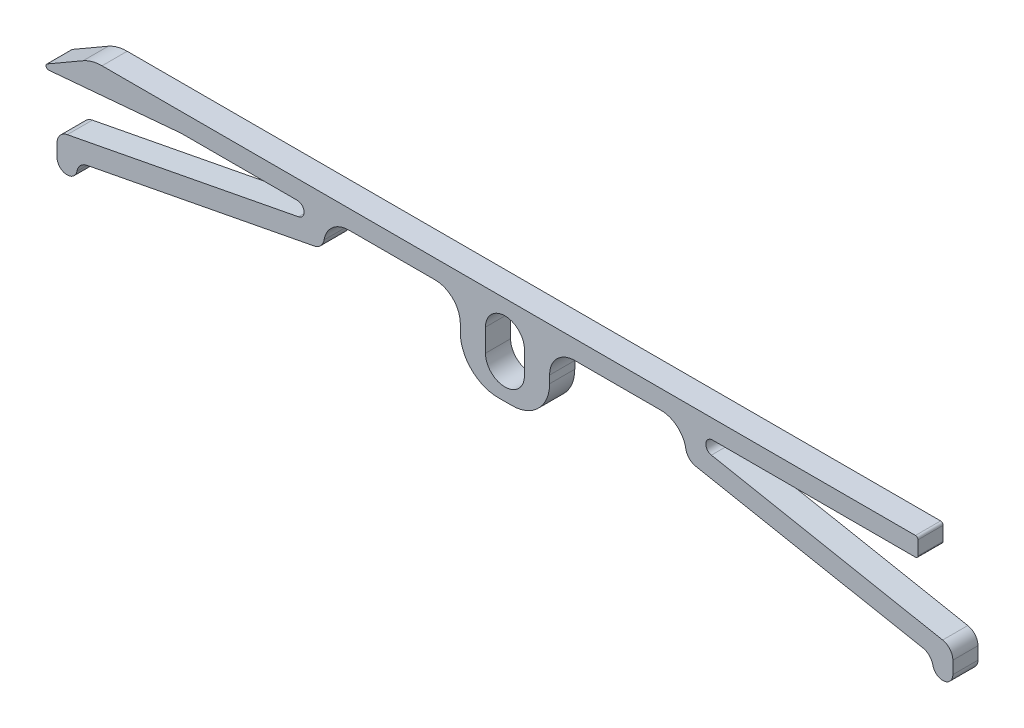
SolidWorks part; units mm, degrees
other "Static 1"
material "AISI 304"
ref_plane "Front Plane" through (0, 0, 0) normal (0, 0, 1) x (1, 0, 0)
ref_plane "Top Plane" through (0, 0, 0) normal (0, 1, 0) x (1, 0, 0)
ref_plane "Right Plane" through (0, 0, 0) normal (1, 0, 0) x (0, 0, -1)
sketch "Sketch1" plane through (0, 0, 0) normal (0, 0, 1) x (1, 0, 0)
  line L0 (-33.701, 0) -> (33.701, 0)
  line L1 (-33.701, 0) -> (-36.299, -1.5)
  line L2 (-36.299, -1.5) -> (-14.299, -1.5)
  line L3 (33.701, -1.5) -> (33.701, 0)
  line L4 (0, 0) -> (0, -18.161) construction
  line L5 (-11.2966, -1.5) -> (-33.3629, -7.6) construction
  line L6 (-14.299, -1.5) -> (-33.576, -6.8289)
  line L7 (-8.2941, -1.5) -> (-33.1497, -8.3711)
  line L8 (-11.5097, -0.7289) -> (-33.576, -6.8289) construction
  line L9 (-11.0834, -2.2711) -> (-33.1497, -8.3711) construction
  line L10 (-8.2941, -1.5) -> (-2.5, -1.5)
  line L11 (-14.299, -1.5) -> (-13.8727, -3.0422) construction
  line L12 (-36.299, -1.5) -> (-36.299, -9.185) construction
  line L13 (-2.5, -1.5) -> (-2.5, -6.6)
  line L14 (-2.5, -6.6) -> (2.5, -6.6)
  line L15 (2.5, -6.6) -> (2.5, -1.5)
  line L16 (0, -4.1) -> (0, -2.5) construction
  line L17 (-1.5, -4.1) -> (-1.5, -2.5)
  line L18 (1.5, -4.1) -> (1.5, -2.5)
  line L19 (2.5, -1.5) -> (8.2941, -1.5)
  line L20 (-35.2417, -8.4) -> (-31.484, -8.4) construction
  line L21 (8.2941, -1.5) -> (33.1497, -8.3711)
  line L22 (14.299, -1.5) -> (33.576, -6.8289)
  line L23 (14.299, -1.5) -> (33.701, -1.5)
  arc A1 (-33.576, -6.8289) -> (-33.1497, -8.3711) centre (-33.3629, -7.6) ccw
  arc A2 (-1.5, -4.1) -> (1.5, -4.1) centre (0, -4.1) ccw
  arc A3 (1.5, -2.5) -> (-1.5, -2.5) centre (0, -2.5) ccw
  arc A4 (33.576, -6.8289) -> (33.1497, -8.3711) centre (33.3629, -7.6) cw
  point P21 (0, -6.6)
  point P24 (0, -3.3)
  point P29 (-33.3629, -8.4)
  point P31 (0, -5.6)
  point P33 (0, -1)
  dimension "D1" = 70
  dimension "D2" = 1.5
  dimension "D3" = 30
  dimension "D6" = 20
  dimension "D7" = 22
  dimension "D8" = 3
  dimension "D9" = 1.6
  dimension "D10" = 1
  dimension "D11" = 1
  dimension "D12" = 1
  dimension "D13" = 1.8
  dimension "D14" = 8.4
  dimension "D4" = 0.8
  dimension "D5" = 0.8
sketch "Sketch2" plane through (0, 0, 0) normal (0, 0, 1) x (1, 0, 0)
  line L0 (-32.8349, 0) -> (32.8349, 0)
  line L1 (-32.8349, 0) -> (-37.1651, -2.5)
  line L2 (-25.735, -1.5) -> (32.8349, -1.5)
  line L3 (32.8349, -1.5) -> (32.8349, 0)
  line L4 (-25.735, -1.5) -> (-37.1651, -2.5)
  dimension "D1" = 70
  dimension "D2" = 1.5
  dimension "D3" = 30
  dimension "D4" = 2.5
  dimension "D5" = 25
extrude "flat" add sketch "Sketch2" along normal blind 2
sketch "Sketch3" plane through (0, 0, 0) normal (0, 0, -1) x (-1, 0, 0)
  line L0 (-32.8349, 0) -> (32.8349, 0) construction
  line L1 (3.55, 0) -> (-3.55, 0)
  line L2 (3.55, 0) -> (3.55, -7.1)
  line L3 (3.55, -7.1) -> (-3.55, -7.1)
  line L4 (-3.55, 0) -> (-3.55, -7.1)
  line L5 (0, -2.75) -> (0, -4.55) construction
  line L6 (1.55, -2.75) -> (1.55, -4.55) construction
  line L7 (-1.55, -2.75) -> (-1.55, -4.55) construction
  arc A0 (1.55, -2.75) -> (-1.55, -2.75) centre (0, -2.75) ccw construction
  arc A1 (-1.55, -4.55) -> (1.55, -4.55) centre (0, -4.55) ccw construction
  point P6 (0, -3.65)
  point P14 (0, -1.2)
  point P15 (1.55, -3.65)
  point P16 (0, -6.1)
  dimension "D1" = 1.8
  dimension "D2" = 1.2
  dimension "D3" = 3.1
extrude "Boss-Extrude3" add sketch "Sketch3" against normal up to surface (2 mm away) up to face at (-6.013, -1.1, 2)
sketch "Sketch4" plane through (0, 0, 2) normal (0, 0, 1) x (1, 0, 0)
  line L0 (-1.55, -2.75) -> (-1.55, -4.55) construction
  line L1 (1.55, -2.75) -> (1.55, -4.55) construction
  line L2 (-1.55, -2.75) -> (-1.55, -4.55)
  line L3 (1.55, -2.75) -> (1.55, -4.55)
  arc A0 (-1.55, -4.55) -> (1.55, -4.55) centre (0, -4.55) ccw construction
  arc A1 (1.55, -2.75) -> (-1.55, -2.75) centre (0, -2.75) ccw construction
  arc A2 (-1.55, -4.55) -> (1.55, -4.55) centre (0, -4.55) ccw
  arc A3 (1.55, -2.75) -> (-1.55, -2.75) centre (0, -2.75) ccw
extrude "Cut-Extrude1" cut sketch "Sketch4" against normal through all both and the other way through all
sketch "Sketch5" [suppressed] plane through (0, 0, 0) normal (0, 0, -1) x (-1, 0, 0)
  line L0 (7.7863, -1.5) -> (34.2564, -8.1) construction
  line L1 (25.735, -1.5) -> (3.55, -1.5) construction
  line L2 (4.4796, -1.5) -> (34.0629, -8.8762)
  line L3 (15.0441, -2.4851) -> (34.45, -7.3238)
  line L4 (15.1651, -1.5) -> (15.3651, -1.5)
  line L5 (15.3651, -1.5) -> (15.3651, 0)
  line L6 (15.3651, 0) -> (4.2796, 0)
  line L7 (4.2796, 0) -> (4.2796, -1.5)
  line L8 (7.5928, -2.2762) -> (34.0629, -8.8762) construction
  line L9 (4.2796, -1.5) -> (4.4796, -1.5)
  line L10 (7.9799, -0.7238) -> (34.45, -7.3238) construction
  line L11 (-32.8349, 0) -> (32.8349, 0) construction
  line L12 (15.1651, -2) -> (14.657, -4.0376) construction
  line L13 (37.7236, -8.9) -> (30.7892, -8.9) construction
  line L14 (-3.55, -7.1) -> (3.55, -7.1) construction
  arc A1 (34.0629, -8.8762) -> (34.45, -7.3238) centre (34.2564, -8.1) ccw
  arc A2 (15.0441, -2.4851) -> (15.1651, -1.5) centre (15.1651, -2) cw
  point P24 (34.2564, -8.9)
  dimension "D3" = 0.5
  dimension "D5" = 0.2
  dimension "D7" = 20
  dimension "D8" = 1.8
  dimension "D6" = 22
  dimension "D1" = 0.8
  dimension "D2" = 0.8
extrude "Boss-Extrude4" [suppressed] add sketch "Sketch5" against normal up to surface (2 mm away)
mirror "Mirror3" [suppressed] about plane through (0, 0, 0) normal (1, 0, 0)
fillet "Fillet1" [suppressed] radius 10
fillet "Fillet2" [suppressed] radius 0.5
sketch "Sketch6" plane through (0, 0, 2) normal (0, 0, 1) x (1, 0, 0)
  line L0 (-15.1651, -1.5) -> (-15.1651, -3.1608) construction
  line L1 (-25.735, -1.5) -> (-3.55, -1.5) construction
  line L2 (-15.1651, -3.1608) -> (-34.8049, -6.9392) construction
  line L3 (-34.8049, -6.9392) -> (-34.8049, -8.1) construction
  line L4 (-15.9651, -1.5) -> (-15.9651, -2.5) construction
  line L5 (-16.4093, -2.5855) -> (-35.6049, -6.2785)
  line L6 (-35.6049, -6.2785) -> (-35.6049, -8.1)
  line L7 (-14.3651, -1.5) -> (-14.3651, -3.8215)
  line L8 (-14.3651, -3.8215) -> (-34.0049, -7.6)
  line L9 (-34.0049, -7.6) -> (-34.0049, -8.1)
  line L10 (-16.5127, -1.5) -> (-14.3651, -1.5)
  line L11 (-15.9651, -2.5) -> (-35.6049, -6.2785) construction
  line L13 (-35.2532, -8.9) -> (-34.3566, -8.9) construction
  line L14 (3.55, -7.1) -> (-3.55, -7.1) construction
  arc A1 (-35.6049, -8.1) -> (-34.0049, -8.1) centre (-34.8049, -8.1) ccw
  arc A2 (-16.4093, -2.5855) -> (-16.5127, -1.5) centre (-16.5127, -2.0477) ccw
  point P17 (-34.8049, -8.9)
  dimension "D6" = 20
  dimension "D7" = 22
  dimension "D8" = 1.8
  dimension "D1" = 0.8
  dimension "D2" = 0.8
  dimension "D5" = 0.5477
  dimension "D4" = 0.5
extrude "Boss-Extrude5" add sketch "Sketch6" against normal up to surface (2 mm away) up to face at (0, -3.65, 0)
mirror "Mirror4" about plane through (0, 0, 0) normal (1, 0, 0) of "Boss-Extrude5"
fillet "Fillet3" radius 1 6 edges at (-35.6049, -6.2785, 1) (-34.0049, -7.6, 1) (-14.3651, -3.8215, 1) (35.6049, -6.2785, 1) (34.0049, -7.6, 1) (14.3651, -3.8215, 1)
fillet "Fillet4" radius 2 2 edges at (-14.3651, -1.5, 1) (14.3651, -1.5, 1)
fillet "Fillet8" radius 2 2 edges at (3.55, -1.5, 1) (-3.55, -1.5, 1)
fillet "Fillet6" radius 0.2 3 edges at (-37.1651, -2.5, 1) (32.8349, -1.5, 1) (32.8349, 0, 1)
fillet "Fillet7" radius 3 4 edges at (3.55, -7.1, 1) (-3.55, -7.1, 1) (-32.8349, 0, 1) (-25.735, -1.5, 1)
ref_plane "targetPlane" through (0, -7.3, 0) normal (0, -1, 0) x (-1, 0, 0)
equation "\"sheetThickness\"= 2mm"
equation "\"beamHeight\"= 1.6"
equation "\"beamLength\"= 20mm"
equation "\"flatHeight\"= 1.5mm"
equation "\"slotMargin\"= 1mm"
equation "\"tabAllowance\"= 0.2mm"
equation "\"deflection\"= 1.6mm"
equation "\"D10@Sketch1\"=\"slotMargin\""
equation "\"D11@Sketch1\"=\"slotMargin\""
equation "\"D12@Sketch1\"=\"slotMargin\""
equation "\"D9@Sketch1\"=\"deflection\""
equation "\"D4@Sketch1\"=\"beamHeight\"/2"
equation "\"D6@Sketch1\"=\"beamLength\""
equation "\"D13@Sketch1\"=\"deflection\"+\"tabAllowance\""
equation "\"D2@Sketch2\"=\"flatHeight\""
equation "\"D1@flat\" = \"sheetThickness\""
equation "\"D1@Sketch3\"=\"deflection\"+0.2"
equation "\"D5@Sketch3\"=\"slotMargin\""
equation "\"D1@Sketch5\"=\"beamHeight\"/2"
equation "\"cutterDiameter\"= 0.8mm"
equation "\"cutterMargin_diametric\"= 0.2mm"
equation "\"filletRadius_min\"= ( \"cutterDiameter\" + \"cutterMargin_diametric\" ) / 2"
equation "\"D3@Sketch5\"=\"filletRadius_min\""
equation "\"D1@Fillet2\"=\"filletRadius_min\""
equation "\"D1@Sketch6\"=\"beamHeight\"/2"
equation "\"D3@Sketch6\"=\"filletRadius_min\"*2"
equation "\"D4@Sketch6\"=\"filletRadius_min\""
equation "\"D6@Sketch6\"=\"beamLength\""
equation "\"D1@Fillet3\"=\"filletRadius_min\"*2"
equation "\"D7@Sketch6\"=\"beamLength\"+2"
equation "\"D6@Sketch5\"=\"beamLength\"+2"
